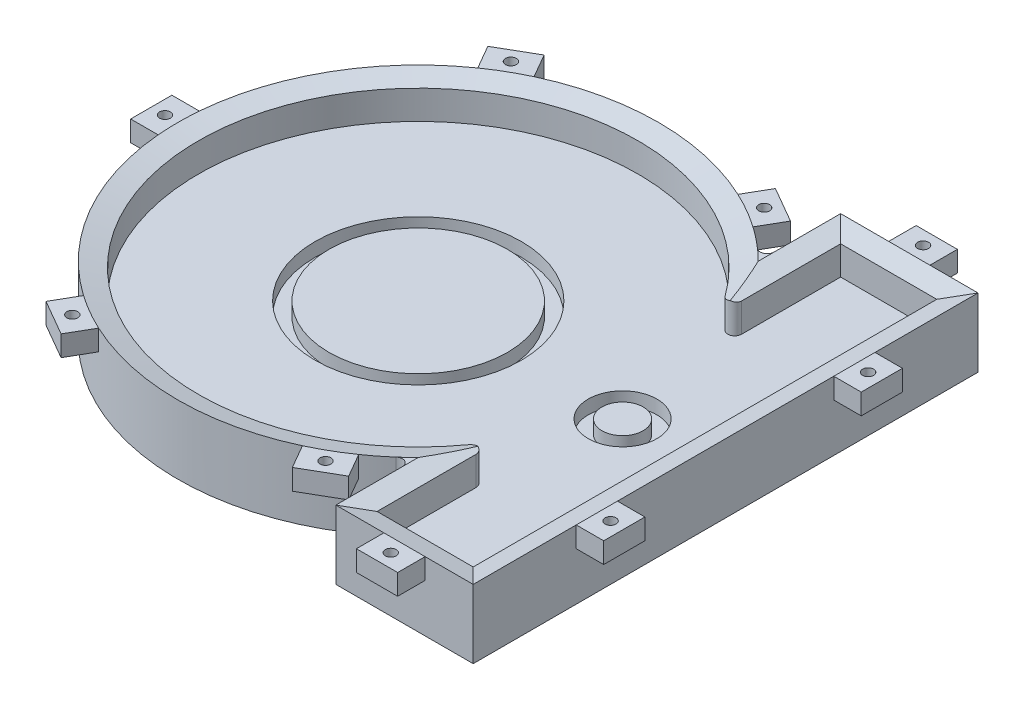
SolidWorks part; units mm, degrees
ref_plane "Front Plane" through (0, 0, 0) normal (0, 0, 1) x (1, 0, 0)
ref_plane "Top Plane" through (0, 0, 0) normal (0, 1, 0) x (1, 0, 0)
ref_plane "Right Plane" through (0, 0, 0) normal (1, 0, 0) x (0, 0, -1)
sketch "Sketch1" plane through (0, 0, 0) normal (0, 1, 0) x (1, 0, 0)
  line L0 (24.7487, 24.7487) -> (24.7487, 36.7487)
  line L1 (50, 50) -> (-50, 50) construction
  line L2 (50, 50) -> (50, -50) construction
  line L3 (50, -50) -> (-50, -50) construction
  line L4 (-50, 50) -> (-50, -50) construction
  line L5 (50, 50) -> (-50, -50) construction
  line L6 (50, -50) -> (-50, 50) construction
  line L7 (24.7487, 36.7487) -> (44.7487, 36.7487)
  line L8 (44.7487, 36.7487) -> (44.7487, -36.7487)
  line L9 (0, 0) -> (50, 0) construction
  line L10 (24.7487, -36.7487) -> (44.7487, -36.7487)
  line L11 (24.7487, -24.7487) -> (24.7487, -36.7487)
  arc A1 (24.7487, 24.7487) -> (24.7487, -24.7487) centre (0, 0) ccw
  circle A3 centre (0, 0) radius 15
  circle A4 centre (30.7487, 0) radius 5 construction
  point P0 (0, 0)
  point P13 (44.7487, 0)
  dimension "D3" = 70
  dimension "D6" = 30
  dimension "D7" = 10
  dimension "D1" = 100
  dimension "D2" = 100
  dimension "D4" = 12
  dimension "D5" = 20
  dimension "D8" = 14
extrude "Boss-Extrude1" add sketch "Sketch1" along normal blind 5
sketch "Sketch2" plane through (0, 5, 0) normal (0, 1, 0) x (1, 0, 0)
  line L0 (24.7487, 24.7487) -> (24.7487, 36.7487)
  line L1 (24.7487, -24.7487) -> (24.7487, -36.7487)
  line L2 (24.7487, -36.7487) -> (44.7487, -36.7487) construction
  line L3 (24.7487, 36.7487) -> (44.7487, 36.7487)
  line L4 (44.7487, 36.7487) -> (44.7487, -36.7487)
  line L5 (24.7487, -36.7487) -> (44.7487, -36.7487)
  line L11 (27.7487, -15.9376) -> (27.7487, -33.7487)
  line L12 (27.7487, -33.7487) -> (41.7487, -33.7487)
  line L13 (41.7487, 33.7487) -> (41.7487, -33.7487)
  line L14 (27.7487, 33.7487) -> (41.7487, 33.7487)
  line L15 (27.7487, 15.9376) -> (27.7487, 33.7487)
  arc A2 (24.7487, 24.7487) -> (24.7487, -24.7487) centre (0, 0) ccw
  arc A3 (27.7487, 15.9376) -> (27.7487, -15.9376) centre (0, 0) ccw
  dimension "D1" = 3
extrude "Boss-Extrude2" add sketch "Sketch2" along normal blind 5
fillet "Fillet2" radius 1 2 edges at (24.7487, 5, 24.7487) (24.7487, 5, -24.7487)
chamfer "Chamfer12" distance 3 angle 15 6 edges at (41.7487, 10, 0) (34.7487, 10, 33.7487) (34.7487, 10, -33.7487) (-32, 10, 0) (27.7487, 10, -24.8432) (27.7487, 10, 24.8432) first distance on face at (22.1333, 10, 0)
ref_plane "Plane2" through (0, 10, 0) normal (0, 1, 0) x (1, 0, 0)
sketch "Sketch5" plane through (0, 10, 0) normal (0, 1, 0) x (1, 0, 0)
  line L0 (-45.9218, 0) -> (58.8074, 0) construction
  line L1 (-34.8712, 3) -> (-38.8712, 3)
  line L2 (-38.8712, 3) -> (-38.8712, -3)
  line L3 (-34.8712, -3) -> (-38.8712, -3)
  line L4 (-14.8375, 31.6993) -> (-16.8375, 35.1634)
  line L5 (-16.8375, 35.1634) -> (-22.0337, 32.1634)
  line L6 (-20.0337, 28.6993) -> (-22.0337, 32.1634)
  line L7 (20.0337, 28.6993) -> (22.0337, 32.1634)
  line L8 (22.0337, 32.1634) -> (16.8375, 35.1634)
  line L9 (14.8375, 31.6993) -> (16.8375, 35.1634)
  line L13 (14.8375, -31.6993) -> (16.8375, -35.1634)
  line L14 (16.8375, -35.1634) -> (22.0337, -32.1634)
  line L15 (20.0337, -28.6993) -> (22.0337, -32.1634)
  line L16 (-20.0337, -28.6993) -> (-22.0337, -32.1634)
  line L17 (-22.0337, -32.1634) -> (-16.8375, -35.1634)
  line L18 (-14.8375, -31.6993) -> (-16.8375, -35.1634)
  line L19 (34.8712, 3) -> (38.8712, 3) [skipped]
  line L20 (38.8712, -3) -> (38.8712, 0) [skipped]
  line L21 (34.8712, -3) -> (38.8712, -3) [skipped]
  line L22 (34.7487, 36.7487) -> (34.7487, 40.7487) construction
  line L23 (37.7487, 40.7487) -> (31.7487, 40.7487)
  line L24 (44.7487, 36.7487) -> (24.7487, 36.7487) construction
  line L25 (31.7487, 40.7487) -> (31.7487, 36.7487)
  line L26 (37.7487, 40.7487) -> (37.7487, 36.7487)
  line L27 (44.7487, 18.7487) -> (48.7487, 18.7487) construction
  line L28 (44.7487, -36.7487) -> (44.7487, 36.7487) construction
  line L29 (31.7487, 36.7487) -> (37.7487, 36.7487)
  line L30 (44.7487, 21.7487) -> (48.7487, 21.7487)
  line L31 (48.7487, 21.7487) -> (48.7487, 15.7487)
  line L32 (44.7487, 15.7487) -> (48.7487, 15.7487)
  line L33 (44.7487, 21.7487) -> (44.7487, 15.7487)
  line L34 (48.7487, -21.7487) -> (48.7487, -15.7487)
  line L35 (44.7487, -21.7487) -> (48.7487, -21.7487)
  line L36 (44.7487, -21.7487) -> (44.7487, -15.7487)
  line L37 (44.7487, -15.7487) -> (48.7487, -15.7487)
  line L38 (31.7487, -36.7487) -> (37.7487, -36.7487)
  line L39 (37.7487, -40.7487) -> (37.7487, -36.7487)
  line L40 (31.7487, -40.7487) -> (31.7487, -36.7487)
  line L41 (37.7487, -40.7487) -> (31.7487, -40.7487)
  arc A0 (-34.8712, 3) -> (-34.8712, -3) centre (0, 0) ccw
  circle A1 centre (-36.8712, 0) radius 0.7937
  circle A2 centre (-18.4356, 31.9314) radius 0.7937
  arc A3 (23.0891, 26.3039) -> (23.0891, -26.3039) centre (0, 0) ccw construction
  circle A4 centre (18.4356, 31.9314) radius 0.7937
  circle A6 centre (18.4356, -31.9314) radius 0.7937
  circle A7 centre (-18.4356, -31.9314) radius 0.7938
  arc A8 (-14.8375, 31.6993) -> (-20.0337, 28.6993) centre (0, 0) ccw
  arc A9 (20.0337, 28.6993) -> (14.8375, 31.6993) centre (0, 0) ccw
  arc A11 (14.8375, -31.6993) -> (20.0337, -28.6993) centre (0, 0) ccw
  arc A12 (-20.0337, -28.6993) -> (-14.8375, -31.6993) centre (0, 0) ccw
  arc A13 (37.6649, 0) -> (36.0774, 0) centre (36.8712, 0) ccw [skipped]
  circle A14 centre (34.7487, 38.7487) radius 0.795
  circle A15 centre (46.7487, 18.7487) radius 0.795
  circle A16 centre (46.7487, -18.7487) radius 0.795
  circle A17 centre (34.7487, -38.7487) radius 0.795
  point P9 (-38.8712, 0)
  point P48 (0, 0)
  dimension "D3" = 6
  dimension "D4" = 1.5875
  dimension "D9" = 1.59
  dimension "D12" = 1.59
  dimension "D1" = 3
  dimension "D2" = 4
  dimension "D5" = 2
  dimension "D6" = 3
  dimension "D7" = 4
  dimension "D8" = 18
  dimension "D10" = 3
  dimension "D11" = 4
extrude "Boss-Extrude3" add sketch "Sketch5" against normal blind 3
fillet "Fillet3" radius 1 2 edges at (27.7487, 7.0981, 15.9376) (27.7487, 7.0981, -15.9376)
sketch "Sketch6" plane through (0, 5, 0) normal (0, 1, 0) x (1, 0, 0)
  circle A0 centre (0, 0) radius 15
extrude "Boss-Extrude4" add sketch "Sketch6" against normal blind 5
sketch "Sketch7" plane through (0, 5, 0) normal (0, 1, 0) x (1, 0, 0)
  line L0 (44.7487, -15.7487) -> (44.7487, 15.7487) construction
  line L1 (24.7487, -36.7487) -> (31.7487, -36.7487) construction
  circle A0 centre (0, 0) radius 15
  circle A1 centre (29.7487, 0) radius 5
  circle A2 centre (0, 0) radius 13
  circle A3 centre (29.7487, 0) radius 3
  dimension "D1" = 30
  dimension "D2" = 10
  dimension "D3" = 15
  dimension "D4" = 36.7487
  dimension "D5" = 2
extrude "Cut-Extrude1" cut sketch "Sketch7" against normal blind 2
